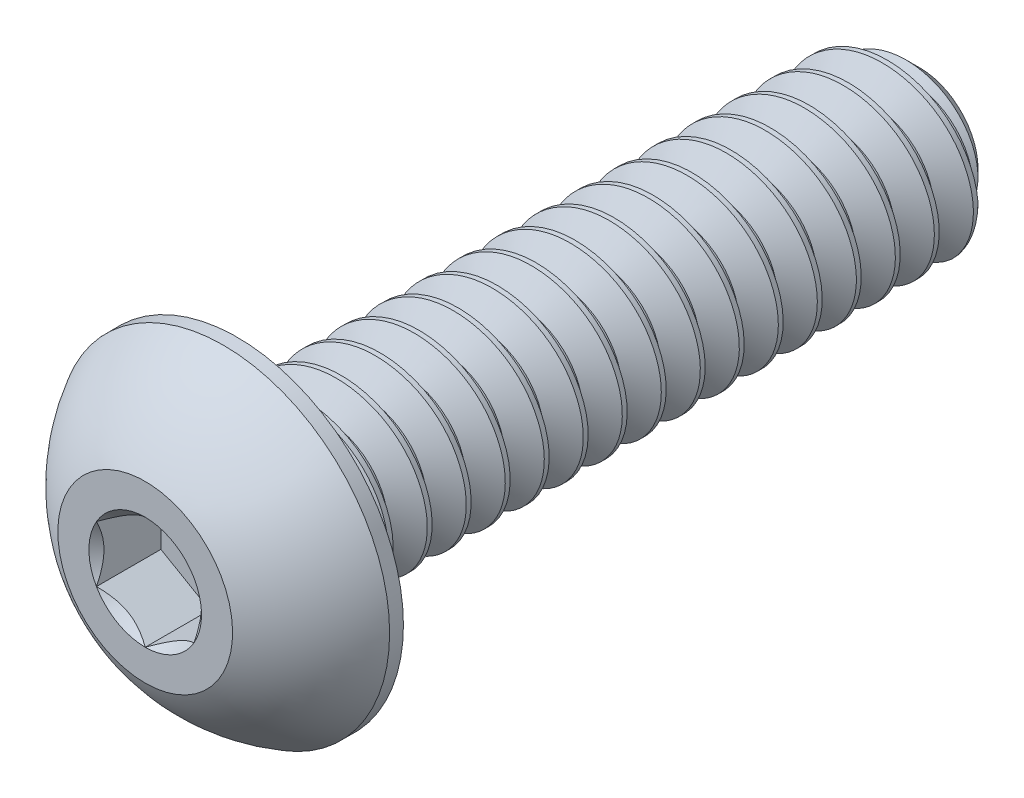
SolidWorks part; units mm, degrees
material "AISI 316 Stainless Steel Sheet (SS)"
ref_plane "Front" through (0, 0, 0) normal (0, 0, 1) x (1, 0, 0)
ref_plane "Top" through (0, 0, 0) normal (0, 1, 0) x (1, 0, 0)
ref_plane "Right" through (0, 0, 0) normal (1, 0, 0) x (0, 0, -1)
sketch "Sketch1" plane through (0, 0, 0) normal (1, 0, 0) x (0, 0, -1)
  line L2 (1.4986, 1.4224) -> (12.6111, 1.4224)
  line L3 (12.6111, 1.4224) -> (12.6111, 0)
  line L4 (12.6111, 0) -> (1.4986, 0)
  line L6 (1.2738, 2.7051) -> (1.4986, 2.7051) construction
  line L7 (12.6111, 1.4224) -> (12.6111, -1.4224) construction
  line L8 (0, 0) -> (1.4986, 0) construction
  line L9 (1.4986, 2.7051) -> (1.4986, -2.7051) construction
  line L11 (1.4986, 1.4224) -> (1.4986, 0)
  line L13 (0, 0.7937) -> (0, -0.7937) construction
  line L14 (0, 0.7937) -> (0, 1.4224) construction
  arc A3 (0, 1.4224) -> (1.2738, 2.7051) centre (2.7151, 0) cw construction
  dimension "D1" = 0.2248
  dimension "Head Ht" = 1.4986
  dimension "Head Dia" = 5.4102
  dimension "Dia" = 2.8448
  dimension "Lg" = 11.1125
  dimension "Hex" = 1.5875
revolve "Revolve1" add sketch "Sketch1" angle 360 mid plane about L4
sketch "Sketch3" plane through (0, 0, -12.6111) normal (0, 0, -1) x (-1, 0, 0)
  circle A0 centre (0, 0) radius 1.4224
curve "Helix/Spiral1" pitch 0.635 height 12.6111 radius 1.4224 centre (0, 0, -12.6111) axis (0, 0, 1) start towards (0, 1, 0)
sketch "Sketch2" plane through (0, 0, 0) normal (1, 0, 0) x (0, 0, -1)
  line L0 (12.6111, 1.4224) -> (13.1667, 1.4224)
  line L1 (13.1667, 1.4224) -> (12.9286, 1.01)
  line L2 (12.9286, 1.01) -> (12.8492, 1.01)
  line L3 (12.8492, 1.01) -> (12.6111, 1.4224)
  line L4 (12.7302, 1.2162) -> (13.0477, 1.2162) construction
  dimension "D1" = 60
  dimension "D2" = 0.0794
  dimension "D3" = 0.3175
chamfer "Chamfer1" distance 0.4763 angle 45 1 edges at (0, 1.4224, -12.6111)
sweep "Cut-Sweep1" cut profiles "Sketch2" path "Helix/Spiral1" align with end faces yes
sketch "Sketch7" plane through (0, 0, 0) normal (1, 0, 0) x (0, 0, -1)
  line L6 (1.2738, 2.7051) -> (1.4986, 2.7051) construction
  line L8 (0, 0) -> (1.4986, 0) construction
  line L11 (1.4986, 2.7051) -> (1.4986, -2.7051) construction
  line L12 (1.2738, 2.7051) -> (1.4986, 2.7051)
  line L13 (0, 0) -> (1.4986, 0)
  line L14 (0, 0.7937) -> (0, -0.7937) construction
  line L15 (1.4986, 2.7051) -> (1.4986, 0)
  line L16 (0, 1.4224) -> (0, 0)
  arc A2 (1.2738, 2.7051) -> (0, 1.4224) centre (2.7151, 0) ccw construction
  arc A3 (1.2738, 2.7051) -> (0, 1.4224) centre (2.7151, 0) ccw
revolve "Revolve2" add sketch "Sketch7" angle 360 mid plane about L13
sketch "Sketch5" plane through (0, 0, 0) normal (0, 0, 1) x (1, 0, 0)
  line L1 (0.7937, -0.4583) -> (0.7937, 0.4583)
  line L2 (0.7937, 0.4583) -> (0, 0.9165)
  line L3 (0, 0.9165) -> (-0.7938, 0.4583)
  line L4 (-0.7938, 0.4583) -> (-0.7937, -0.4583)
  line L5 (-0.7937, -0.4583) -> (0, -0.9165)
  line L6 (0, -0.9165) -> (0.7937, -0.4583)
  circle A0 centre (0, 0) radius 0.7937 construction
extrude "Cut-Extrude2" cut sketch "Sketch5" against normal blind 1.049
sketch "Sketch6" plane through (0, 0, 0) normal (0, 0, 1) x (1, 0, 0)
  circle A0 centre (0, 0) radius 0.9165
extrude "Cut-Extrude3" cut sketch "Sketch6" against normal blind 1.049 draft 45
sketch "Sketch9" [suppressed] plane through (0, 0, -1.4986) normal (0, 0, 1) x (1, 0, 0)
  circle A2 centre (0, 0) radius 1.4224
extrude "Boss-Extrude2" [suppressed] add sketch "Sketch9" against normal offset from surface (6.35 mm away) 22.225 up to face at (0, 0.9462, -12.6111)
sketch "Sketch10" plane through (0, 0, 0) normal (1, 0, 0) x (0, 0, -1)
  line L0 (12.6111, 1.4224) -> (12.6111, -1.4224) construction
  point P0 (11.6586, -1.4224)
  dimension "D1" = 0.9525
equation "\"D3@Helix/Spiral1\" = \"Lg@Sketch1\" + \"Head Ht@Sketch1\""
equation "\"D2@Sketch2\" = \"D4@Helix/Spiral1\" * .125"
equation "\"D3@Sketch2\" = \"D4@Helix/Spiral1\" * .5"
equation "\"D1@Chamfer1\" = \"D4@Helix/Spiral1\" * .75"
equation "\"D1@Cut-Extrude2\" = \"Head Ht@Sketch1\" * .7"
equation "\"D1@Sketch1\" = \"Head Ht@Sketch1\" * .15"
equation "\"D1@Sketch10\" = \"D4@Helix/Spiral1\" * 1.5"
equation "\"D1@Cut-Extrude3\" = \"D1@Cut-Extrude2\""
